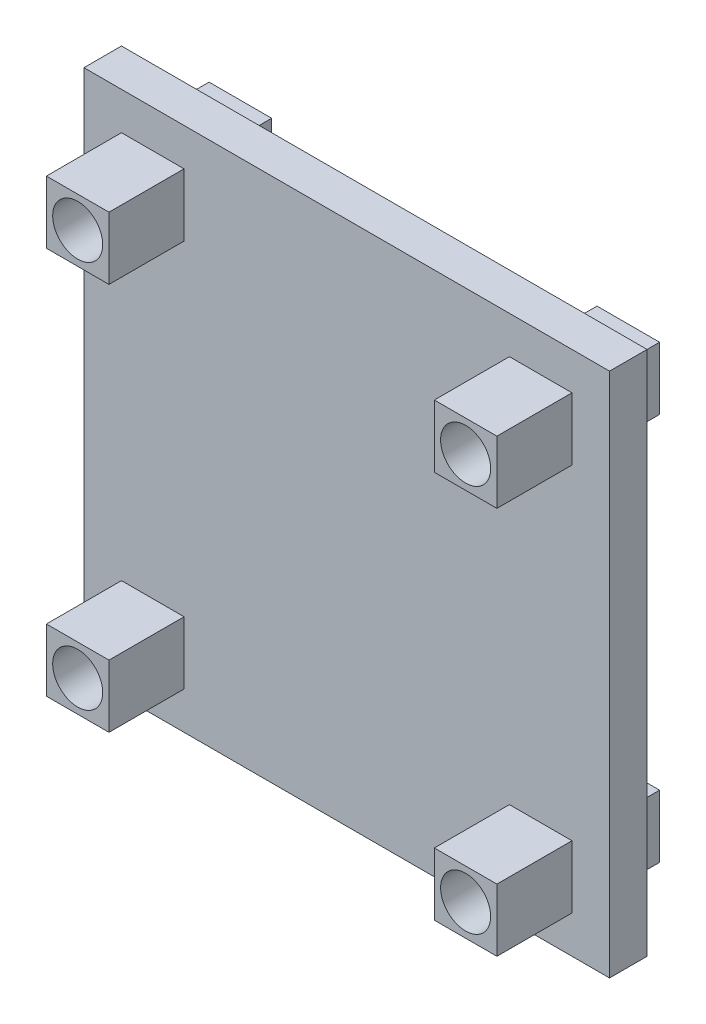
SolidWorks part; units mm, degrees
ref_plane "Front Plane" through (0, 0, 0) normal (0, 0, 1) x (1, 0, 0)
ref_plane "Top Plane" through (0, 0, 0) normal (0, 1, 0) x (1, 0, 0)
ref_plane "Right Plane" through (0, 0, 0) normal (1, 0, 0) x (0, 0, -1)
sketch "Sketch2" plane through (0, 0, 0) normal (0, 0, 1) x (1, 0, 0)
  line L0 (0, -55) -> (0, 55) construction
  line L1 (-21, -21) -> (21, -21)
  line L2 (-21, -21) -> (-21, 21)
  line L3 (-21, 21) -> (21, 21)
  line L4 (21, -21) -> (21, 21)
  line L5 (-21, -21) -> (21, 21) construction
  line L6 (-21, 21) -> (21, -21) construction
  line L7 (-20, -20) -> (20, -20)
  line L8 (-20, -20) -> (-20, 20)
  line L9 (-20, 20) -> (20, 20)
  line L10 (20, -20) -> (20, 20)
  line L11 (-20, -20) -> (20, 20) construction
  line L12 (-20, 20) -> (20, -20) construction
  line L13 (-15.5, -15.5) -> (15.5, -15.5) construction
  line L14 (-15.5, -15.5) -> (-15.5, 15.5) construction
  line L15 (-15.5, 15.5) -> (15.5, 15.5) construction
  line L16 (15.5, -15.5) -> (15.5, 15.5) construction
  line L17 (-15.5, -15.5) -> (15.5, 15.5) construction
  line L18 (-15.5, 15.5) -> (15.5, -15.5) construction
  line L19 (-18, 13) -> (-13, 13)
  line L20 (-18, 13) -> (-18, 18)
  line L21 (-18, 18) -> (-13, 18)
  line L22 (-13, 13) -> (-13, 18)
  line L23 (-18, 13) -> (-13, 18) construction
  line L24 (-18, 18) -> (-13, 13) construction
  line L25 (18, 13) -> (18, 18)
  line L26 (18, 13) -> (13, 13)
  line L27 (13, 13) -> (13, 18)
  line L28 (18, 18) -> (13, 18)
  line L29 (55, 0) -> (-55, 0) construction
  line L30 (18, -13) -> (13, -13)
  line L31 (18, -13) -> (18, -18)
  line L32 (18, -18) -> (13, -18)
  line L33 (13, -13) -> (13, -18)
  line L34 (-18, -13) -> (-18, -18)
  line L35 (-18, -13) -> (-13, -13)
  line L36 (-13, -13) -> (-13, -18)
  line L37 (-18, -18) -> (-13, -18)
  circle A0 centre (-15.5, 15.5) radius 2
  circle A1 centre (15.5, 15.5) radius 2
  circle A2 centre (15.5, -15.5) radius 2
  circle A3 centre (-15.5, -15.5) radius 2
  point P0 (0, 0)
  point P6 (0, 0)
  point P23 (0, 0)
  dimension "D1" = 42
  dimension "D2" = 42
  dimension "D3" = 40
  dimension "D4" = 5
  dimension "D5" = 5
extrude "Boss-Extrude1" add sketch "Sketch2" along normal blind 3 contours L3 L4 L1 L2
extrude "Boss-Extrude9" add sketch "Sketch2<5>" along normal blind 6 from surface contours L34 L37 L36 L35 A3 | L30 L33 L32 L31 A2 | L25 L28 L27 L26 A1 | L19 L22 L21 L20 A0 | L36 L37 L34 L35 | L30 L33 L32 L31 | L25 L28 L27 L26 | L22 L21 L20 L19 region at (-17.9293, 15.5, 0) region at (15.5, 13.0707, 0) region at (17.9293, -15.5, 0) region at (-15.5, -13.0707, 0) starting at face at (0, 0, 3)
sketch "Sketch2<5>" plane through (0, 0, 0) normal (0, 0, 1) x (1, 0, 0) same geometry as "Sketch2"
extrude "Cut-Extrude3" cut sketch "Sketch2<7>" along normal through all both and the other way through all contours A0 | A1 | A2 | A3
sketch "Sketch2<7>" plane through (0, 0, 0) normal (0, 0, 1) x (1, 0, 0) same geometry as "Sketch2"
extrude "Boss-Extrude10" add sketch "Sketch2<6>" against normal blind 4 from surface contours L34 L37 L36 L35 A3 | L30 L33 L32 L31 A2 | L25 L28 L27 L26 A1 | L19 L22 L21 L20 A0 region at (-17.9293, 15.5, 0) region at (15.5, 13.0707, 0) region at (17.9293, -15.5, 0) region at (-15.5, -13.0707, 0) starting at face at (-17.5, -15.5, 0)
sketch "Sketch2<6>" plane through (0, 0, 0) normal (0, 0, 1) x (1, 0, 0) same geometry as "Sketch2"
ref_plane "Plane3" through (0, 0, 1.5) normal (0, 0, 1) x (1, 0, 0)
